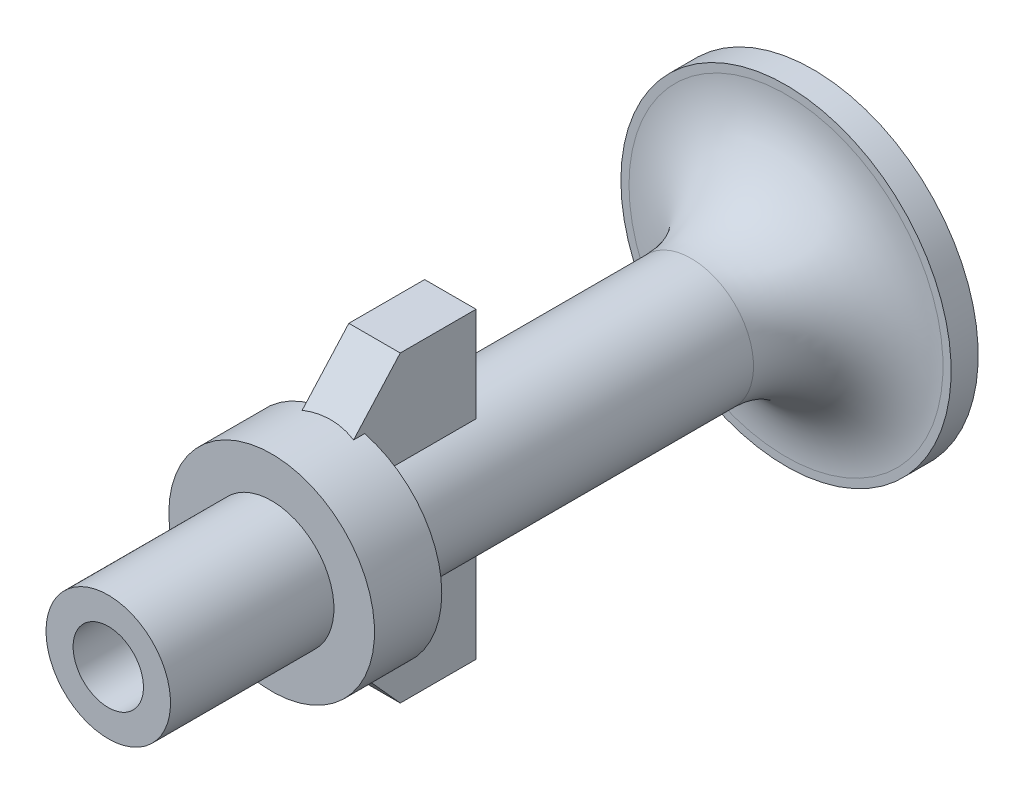
SolidWorks part; units mm, degrees
ref_plane "Спереди" through (0, 0, 0) normal (0, 0, 1) x (1, 0, 0)
ref_plane "Сверху" through (0, 0, 0) normal (0, 1, 0) x (1, 0, 0)
ref_plane "Справа" through (0, 0, 0) normal (1, 0, 0) x (0, 0, -1)
other "Configuration Table"
sketch "Sketch1" plane through (0, 0, 0) normal (1, 0, 0) x (0, 0, -1)
  line L0 (10.4633, 2.3) -> (16.4994, 2.3)
  line L12 (15.3, 0) -> (0, 0) construction
  line L19 (34.7711, 2.7267) -> (36.5, 5.0782)
  line L20 (35.5, 6.1) -> (35.5, 5.8)
  line L21 (36.5, 6.1) -> (35.5, 6.1)
  line L22 (36.5, 5.0782) -> (36.5, 6.1)
  line L23 (16.4994, 2.3) -> (16.4994, 3.8)
  line L24 (16.4994, 3.8) -> (18.9835, 3.8)
  line L25 (18.9835, 3.8) -> (18.9835, 2.3)
  line L26 (32, 2.3) -> (18.9835, 2.3)
  line L27 (31.9513, 1.3) -> (10.4633, 1.3)
  line L28 (10.4633, 2.3) -> (10.4633, 1.3)
  arc A2 (34.7711, 2.7267) -> (31.9513, 1.3) centre (31.9513, 4.8) cw
  arc A3 (35.5, 5.8) -> (32, 2.3) centre (32, 5.8) cw
  point P7 (-6.4246, 0)
  point P47 (15.3, 0)
revolve "Revolve1" add sketch "Sketch1" angle 360 about L12
sketch "Sketch2" plane through (0, 0, 0) normal (1, 0, 0) x (0, 0, -1)
  line L2 (23.1, 1.4607) -> (23.1, 5.6)
  line L3 (23.1, 5.6) -> (20.3, 5.6)
  line L4 (20.3, 5.6) -> (16.5838, 1.4607)
  line L5 (16.5838, 1.4607) -> (23.1, 1.4607)
  line L6 (16.5838, -1.4607) -> (23.1, -1.4607)
  line L7 (20.3, -5.6) -> (16.5838, -1.4607)
  line L8 (23.1, -5.6) -> (20.3, -5.6)
  line L9 (23.1, -1.4607) -> (23.1, -5.6)
extrude "Boss-Extrude1" add sketch "Sketch2" along normal blind 0.95 and the other way blind 0.95
